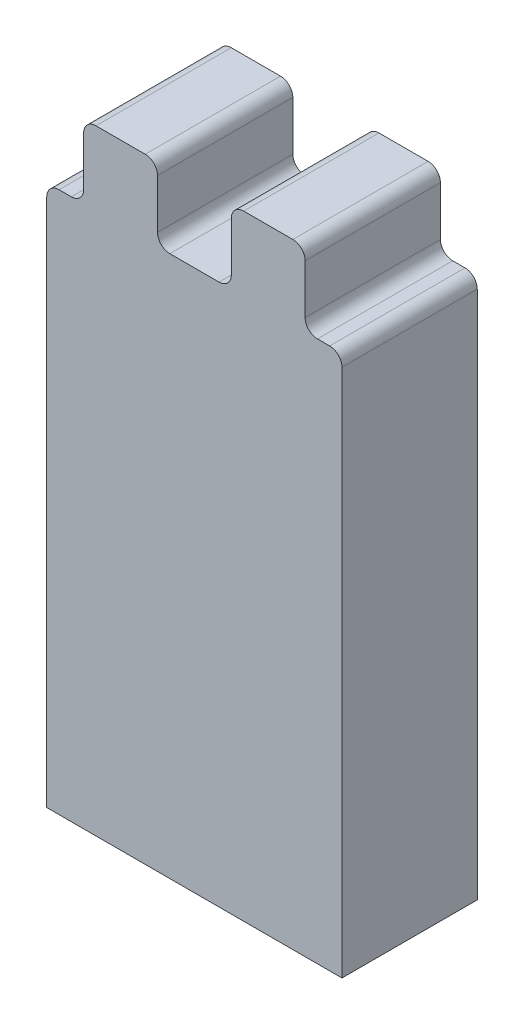
SolidWorks part; units mm, degrees
material "ﾁｰｸ材"
ref_plane "正面" through (0, 0, 0) normal (0, 0, 1) x (1, 0, 0)
ref_plane "平面" through (0, 0, 0) normal (0, 1, 0) x (1, 0, 0)
ref_plane "右側面" through (0, 0, 0) normal (1, 0, 0) x (0, 0, -1)
sketch "ｽｹｯﾁ1" plane through (0, 0, 0) normal (0, 0, 1) x (1, 0, 0)
  line L1 (0, 0) -> (12, 0)
  line L2 (0, 0) -> (0, 25)
  line L3 (0, 25) -> (12, 25)
  line L4 (12, 0) -> (12, 25)
  dimension "D1" = 25
  dimension "D2" = 12
extrude "ﾎﾞｽ - 押し出し1" add sketch "ｽｹｯﾁ1" along normal blind 5.5
sketch "ｽｹｯﾁ2" plane through (0, 0, 5.5) normal (0, 0, 1) x (1, 0, 0)
  line L6 (0, 25) -> (0, 0) construction
  line L7 (0, 25) -> (1.5, 25)
  line L8 (0, 25) -> (0, 22)
  line L9 (0, 22) -> (1.5, 22)
  line L10 (1.5, 25) -> (1.5, 22)
  line L11 (12, 25) -> (0, 25) construction
  line L13 (12, 25) -> (10.5026, 25)
  line L14 (12, 25) -> (12, 22)
  line L15 (12, 22) -> (10.5026, 22)
  line L16 (10.5026, 25) -> (10.5026, 22)
  line L17 (4.5026, 25) -> (7.5026, 25)
  line L18 (4.5026, 25) -> (4.5026, 22)
  line L19 (4.5026, 22) -> (7.5026, 22)
  line L20 (7.5026, 25) -> (7.5026, 22)
  dimension "D1" = 3
  dimension "D2" = 3.0026
  dimension "D3" = 3
  dimension "D4" = 3
  dimension "D5" = 1.5
extrude "ｶｯﾄ - 押し出し1" cut sketch "ｽｹｯﾁ2" against normal through all
fillet "ﾌｨﾚｯﾄ2" radius 0.5 10 edges at (10.5026, 22, 2.75) (10.5026, 25, 2.75) (7.5026, 25, 2.75) (7.5026, 22, 2.75) (4.5026, 22, 2.75) (4.5026, 25, 2.75) (1.5, 25, 2.75) (1.5, 22, 2.75) (12, 22, 2.75) (0, 22, 2.75)
